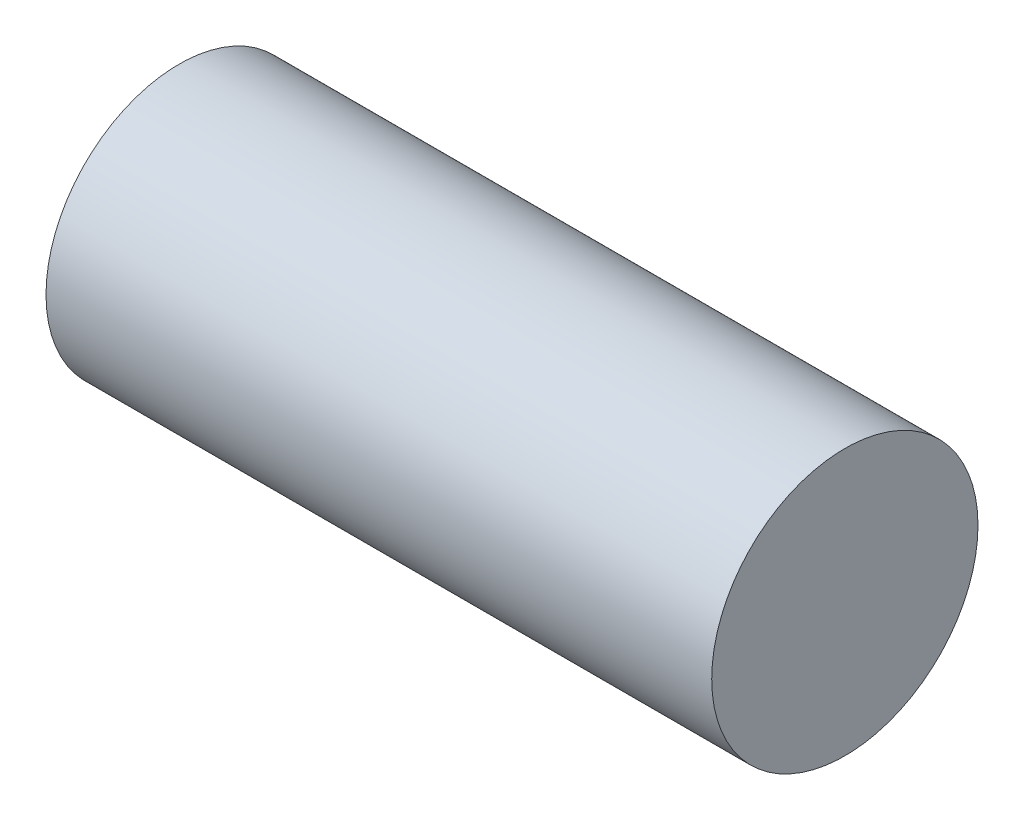
SolidWorks part; units mm, degrees
ref_plane "Front Plane" through (0, 0, 0) normal (1, 0, 0) x (0, 1, 0)
ref_plane "Top Plane" through (0, 0, 0) normal (0, 0, 1) x (0, 1, 0)
ref_plane "Right Plane" through (0, 0, 0) normal (0, 1, 0) x (-1, 0, 0)
sketch "Sketch1" plane through (0, 0, 0) normal (1, 0, 0) x (0, 1, 0)
  circle A0 centre (0, 0) radius 4
  dimension "D1" = 8
extrude "Boss-Extrude1" add sketch "Sketch1" along normal blind 20
